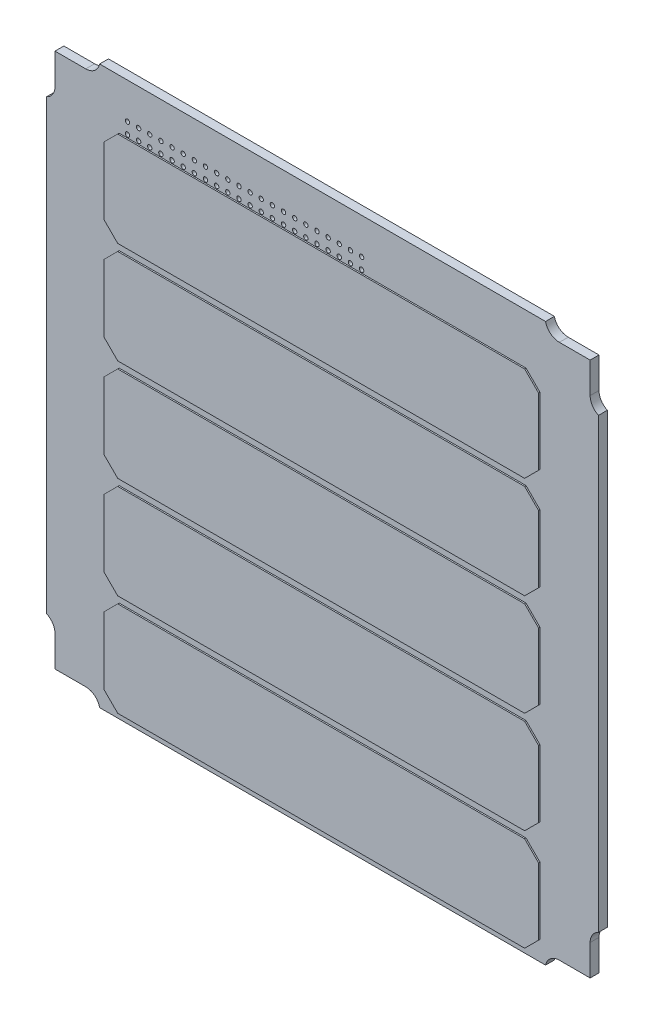
SolidWorks part; units mm, degrees
ref_plane "Front Plane" through (0, 0, 0) normal (0, 0, 1) x (1, 0, 0)
ref_plane "Top Plane" through (0, 0, 0) normal (0, 1, 0) x (1, 0, 0)
ref_plane "Right Plane" through (0, 0, 0) normal (1, 0, 0) x (0, 0, -1)
sketch "Sketch1" plane through (0, 0, 0) normal (0, 0, 1) x (1, 0, 0)
  line L0 (-40, 50) -> (-40, 48)
  line L1 (-50, -50) -> (50, -50)
  line L2 (-50, -50) -> (-50, 50)
  line L3 (-50, 50) -> (50, 50)
  line L4 (50, -50) -> (50, 50)
  line L5 (-50, -50) -> (50, 50) construction
  line L6 (-50, 50) -> (50, -50) construction
  line L7 (-50, 50) -> (-40, 50)
  line L8 (-50, 50) -> (-50, 40)
  line L9 (-40, 48) -> (-48, 48)
  line L10 (-48, 48) -> (-48, 40)
  line L11 (50, 50) -> (40, 50)
  line L12 (50, 50) -> (50, 40)
  line L13 (-48, 40) -> (-50, 40)
  line L14 (50, 40) -> (48, 40)
  line L15 (-50, -50) -> (-37.8649, -50)
  line L16 (-50, -50) -> (-50, -37.8649)
  line L17 (50, 50) -> (50, 40)
  line L18 (50, 50) -> (40, 50)
  line L19 (50, -50) -> (41.5, -50)
  line L20 (50, -50) -> (50, -41.5)
  line L21 (48, 40) -> (48, 48)
  line L22 (48, 48) -> (40, 48)
  line L23 (40, 48) -> (40, 50)
  line L24 (40, -50) -> (40, -48)
  line L25 (50, -50) -> (40, -50)
  line L26 (50, -50) -> (50, -40)
  line L27 (40, -48) -> (48, -48)
  line L28 (48, -48) -> (48, -40)
  line L29 (48, -40) -> (50, -40)
  line L30 (-50, -40) -> (-48, -40)
  line L31 (-50, -50) -> (-50, -40)
  line L32 (-50, -50) -> (-40, -50)
  line L33 (-48, -40) -> (-48, -48)
  line L34 (-48, -48) -> (-40, -48)
  line L35 (-40, -48) -> (-40, -50)
  point P0 (0, 0)
  point P38 (0, 0)
  dimension "D1" = 100
  dimension "D2" = 100
  dimension "D3" = 2
  dimension "D4" = 10
  dimension "D5" = 4
extrude "Boss-Extrude1" add sketch "Sketch1" along normal blind 1.5875 contours L1 L4 L3 L2 region at (0, 0, 0)
sketch "Sketch2" plane through (0, 0, 1.5875) normal (0, 0, 1) x (1, 0, 0)
  line L0 (-36.5, 41) -> (36.5, 41)
  line L1 (-39, 38.5) -> (-36.5, 41)
  line L2 (39, 38.5) -> (39, 26.5)
  line L3 (36.5, 24) -> (-36.5, 24)
  line L4 (-39, 26.5) -> (-39, 38.5)
  line L5 (-36.5, 24) -> (-39, 26.5)
  line L6 (0, 0) -> (0, 50) construction
  line L7 (36.5, 41) -> (39, 38.5)
  line L8 (39, 26.5) -> (36.5, 24)
  line L9 (-36.5, 22.75) -> (36.5, 22.75)
  line L10 (-39, 20.25) -> (-36.5, 22.75)
  line L11 (39, 20.25) -> (39, 8.25)
  line L12 (36.5, 5.75) -> (-36.5, 5.75)
  line L13 (-39, 8.25) -> (-39, 20.25)
  line L14 (-36.5, 5.75) -> (-39, 8.25)
  line L15 (36.5, 22.75) -> (39, 20.25)
  line L16 (39, 8.25) -> (36.5, 5.75)
  line L17 (-36.5, 4.5) -> (36.5, 4.5)
  line L18 (-39, 2) -> (-36.5, 4.5)
  line L19 (39, 2) -> (39, -10)
  line L20 (36.5, -12.5) -> (-36.5, -12.5)
  line L21 (-39, -10) -> (-39, 2)
  line L22 (-36.5, -12.5) -> (-39, -10)
  line L23 (36.5, 4.5) -> (39, 2)
  line L24 (39, -10) -> (36.5, -12.5)
  line L25 (-36.5, -13.75) -> (36.5, -13.75)
  line L26 (-39, -16.25) -> (-36.5, -13.75)
  line L27 (39, -16.25) -> (39, -28.25)
  line L28 (36.5, -30.75) -> (-36.5, -30.75)
  line L29 (-39, -28.25) -> (-39, -16.25)
  line L30 (-40, 50) -> (40, 50) construction
  line L33 (-36.5, -30.75) -> (-39, -28.25)
  line L34 (36.5, -13.75) -> (39, -16.25)
  line L36 (39, -28.25) -> (36.5, -30.75)
  line L37 (-36.5, -32) -> (36.5, -32)
  line L38 (-39, -34.5) -> (-36.5, -32)
  line L39 (39, -34.5) -> (39, -46.5)
  line L40 (36.5, -49) -> (-36.5, -49)
  line L41 (-39, -46.5) -> (-39, -34.5)
  line L42 (-36.5, -49) -> (-39, -46.5)
  line L43 (36.5, -32) -> (39, -34.5)
  line L44 (39, -46.5) -> (36.5, -49)
  line L45 (-40, -50) -> (40, -50) construction
  point P0 (-39, 41)
  point P3 (39, 41)
  point P4 (39, 24)
  point P5 (-39, 24)
  point P19 (-39, 22.75)
  point P21 (39, 22.75)
  point P22 (39, 5.75)
  point P23 (-39, 5.75)
  point P31 (-39, 4.5)
  point P33 (39, 4.5)
  point P34 (39, -12.5)
  point P35 (-39, -12.5)
  point P43 (-39, -13.75)
  point P45 (39, -13.75)
  point P46 (39, -30.75)
  point P47 (-39, -30.75)
  point P55 (-39, -32)
  point P57 (39, -32)
  point P58 (39, -49)
  point P59 (-39, -49)
  dimension "D1" = 78
  dimension "D2" = 17
  dimension "D3" = 5
  dimension "D4" = 1
  dimension "D5" = 9
extrude "Boss-Extrude2" add sketch "Sketch2" along normal blind 0.25
fillet "Fillet1" radius 2.54 8 edges at (-48, -40, 0.7937) (-40, -48, 0.7937) (40, -48, 0.7937) (48, -40, 0.7937) (48, 40, 0.7937) (40, 48, 0.7937) (-40, 48, 0.7937) (-48, 40, 0.7937)
sketch "Sketch5" plane through (0, 0, 1.5875) normal (0, 0, 1) x (1, 0, 0)
  line L0 (0, 50) -> (0, -50) construction
  line L5 (-40, 50) -> (40, 50) construction
  line L6 (-40, -50) -> (40, -50) construction
  line L8 (-35.7478, 50) -> (8.2522, 50) construction
  line L9 (-35.7478, 50) -> (-35.7478, 45.8) construction
  line L10 (-35.7478, 45.8) -> (8.2522, 45.8) construction
  line L11 (8.2522, 50) -> (8.2522, 45.8) construction
  circle A0 centre (-35, 43.55) radius 0.395
  circle A1 centre (-33, 43.55) radius 0.395
  circle A2 centre (-31, 43.55) radius 0.395
  circle A3 centre (-29, 43.55) radius 0.395
  circle A4 centre (-27, 43.55) radius 0.395
  circle A5 centre (-25, 43.55) radius 0.395
  circle A6 centre (-23, 43.55) radius 0.395
  circle A7 centre (-21, 43.55) radius 0.395
  circle A8 centre (-19, 43.55) radius 0.395
  circle A9 centre (-17, 43.55) radius 0.395
  circle A10 centre (-15, 43.55) radius 0.395
  circle A11 centre (-13, 43.55) radius 0.395
  circle A12 centre (-11, 43.55) radius 0.395
  circle A13 centre (-9, 43.55) radius 0.395
  circle A14 centre (-7, 43.55) radius 0.395
  circle A15 centre (-5, 43.55) radius 0.395
  circle A16 centre (-3, 43.55) radius 0.395
  circle A17 centre (-1, 43.55) radius 0.395
  circle A18 centre (1, 43.55) radius 0.395
  circle A19 centre (3, 43.55) radius 0.395
  circle A20 centre (5, 43.55) radius 0.395
  circle A21 centre (7, 43.55) radius 0.395
  circle A22 centre (-33, 41.55) radius 0.395
  circle A23 centre (-31, 41.55) radius 0.395
  circle A24 centre (-29, 41.55) radius 0.395
  circle A25 centre (-27, 41.55) radius 0.395
  circle A26 centre (-25, 41.55) radius 0.395
  circle A27 centre (-23, 41.55) radius 0.395
  circle A28 centre (-21, 41.55) radius 0.395
  circle A29 centre (-19, 41.55) radius 0.395
  circle A30 centre (-17, 41.55) radius 0.395
  circle A31 centre (-15, 41.55) radius 0.395
  circle A32 centre (-13, 41.55) radius 0.395
  circle A33 centre (-11, 41.55) radius 0.395
  circle A34 centre (-9, 41.55) radius 0.395
  circle A35 centre (-7, 41.55) radius 0.395
  circle A36 centre (-5, 41.55) radius 0.395
  circle A37 centre (-3, 41.55) radius 0.395
  circle A38 centre (-1, 41.55) radius 0.395
  circle A39 centre (1, 41.55) radius 0.395
  circle A40 centre (3, 41.55) radius 0.395
  circle A41 centre (5, 41.55) radius 0.395
  circle A42 centre (7, 41.55) radius 0.395
  circle A43 centre (-35, 41.55) radius 0.395
  dimension "D5" = 0.79
  dimension "D2" = 2.25
  dimension "D3" = 2
  dimension "D4" = 2
  dimension "D8" = 1
  dimension "D9" = 44
  dimension "D10" = 4.2
  dimension "D6" = 22
  dimension "D7" = 2
extrude "Cut-Extrude1" cut sketch "Sketch5" against normal through all
sketch "Sketch6" plane through (0, 0, 1.5875) normal (0, 0, 1) x (1, 0, 0)
  line L0 (-40, 50) -> (40, 50) construction
  line L1 (-49.5, 50) -> (49.5, 50)
  line L2 (-49.5, 50) -> (-49.5, -50)
  line L3 (-49.5, -50) -> (49.5, -50)
  line L4 (49.5, 50) -> (49.5, -50)
  line L5 (-40, -50) -> (40, -50) construction
  line L6 (50, -40) -> (50, 40) construction
  dimension "D1" = 99
  dimension "D2" = 0.5
extrude "Cut-Extrude2" cut sketch "Sketch6" against normal through all flip side to cut
